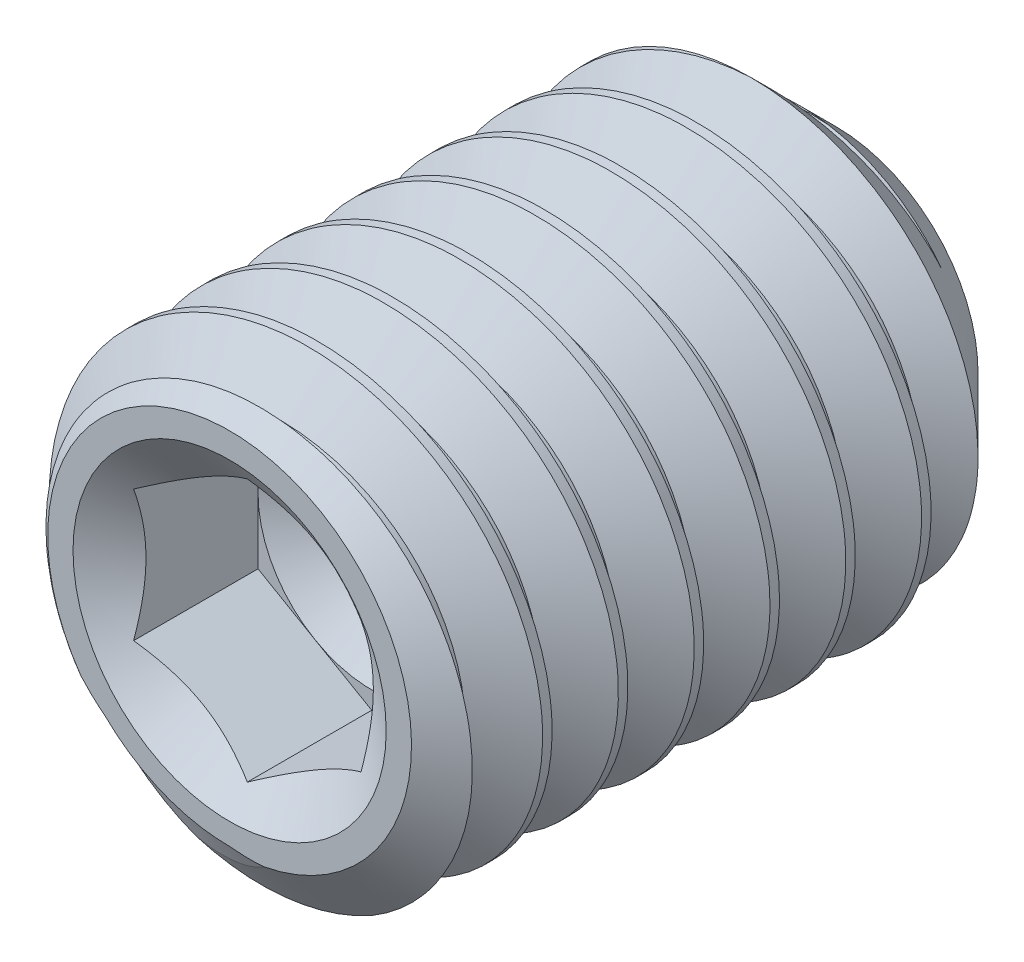
SolidWorks part; units mm, degrees
ref_plane "Front Plane" through (0, 0, 0) normal (0, 0, 1) x (1, 0, 0)
ref_plane "Top Plane" through (0, 0, 0) normal (0, 1, 0) x (1, 0, 0)
ref_plane "Right Plane" through (0, 0, 0) normal (1, 0, 0) x (0, 0, -1)
sketch "Sketch1" plane through (0, 0, 0) normal (1, 0, 0) x (0, 0, -1)
  line L0 (-1.7808, 0) -> (-1.7808, 1.2)
  line L1 (-1.7808, 1.2) -> (-1.5708, 1.5)
  line L2 (-1.5708, 1.5) -> (1.6567, 1.5)
  line L3 (1.6567, 1.5) -> (2.2192, 0.9375)
  line L5 (1.7808, 0) -> (-1.7808, 0)
  line L6 (1.7808, 0) -> (2.2192, 0) construction
  line L7 (2.2192, 0) -> (2.2192, 0.9375) construction
  line L8 (2.2192, -0.9375) -> (1.7808, 0) construction
  line L9 (-1.5708, -1.5) -> (1.6567, -1.5) construction
  line L10 (0, 0) -> (0, -0.5) construction
  line L11 (1.7808, 0) -> (2.112, 0.5512)
  line L12 (1.7808, 0) -> (2.112, -0.5512) construction
  arc A0 (2.112, 0.5512) -> (2.2192, 0.9375) centre (1.4692, 0.9375) ccw
  arc A1 (2.112, -0.5512) -> (2.2192, -0.9375) centre (1.4692, -0.9375) cw construction
  point P11 (-1.7808, 1.5)
  point P12 (0.4692, -1.5)
  point P13 (-0.5308, -1.5)
  point P14 (2.2192, 1.5)
  dimension "D5" = 0.75
  dimension "Thread Size" = 3
  dimension "Length" = 4
  dimension "D3" = 35
  dimension "D6" = 45
  dimension "D7" = 2.4
  dimension "Thread Pitch" = 0.5
  dimension "D2" = 1.25
  dimension "D4" = 59
  dimension "D8" = 1.875
  dimension "D1" = 1.75
sketch "Sketch2" plane through (0, 0, 0) normal (0, 0, 1) x (1, 0, 0)
  line L1 (0.75, 0.433) -> (0, 0.866) construction
  line L2 (0, 0.866) -> (-0.75, 0.433) construction
  line L3 (-0.75, 0.433) -> (-0.75, -0.433) construction
  line L4 (-0.75, -0.433) -> (0, -0.866) construction
  line L5 (0, -0.866) -> (0.75, -0.433) construction
  line L6 (0.75, -0.433) -> (0.75, 0.433) construction
  circle A0 centre (0, 0) radius 0.75 construction
  circle A1 centre (0, 0) radius 1.5 construction
  dimension "Drive Size" = 1.5
sketch "Sketch4" plane through (0, 0, 0) normal (1, 0, 0) x (0, 0, -1)
  line L0 (1.7808, 0) -> (2.112, 0.5512) construction
  line L1 (-1.5708, 1.5) -> (1.6567, 1.5) construction
  line L2 (-1.7808, 0) -> (-1.7808, 1.2) construction
  line L3 (1.7808, 0) -> (-1.7808, 0) construction
  line L4 (1.7808, 0) -> (2.112, 0.5512)
  line L5 (1.6567, 1.5) -> (2.2192, 0.9375) construction
  line L6 (1.6567, 1.5) -> (2.2192, 0.9375)
  line L8 (1.7808, 0) -> (-1.7808, 0)
  line L9 (-1.7808, 0) -> (-1.7808, 1.2)
  line L10 (-1.5708, 1.5) -> (1.6567, 1.5)
  line L11 (-1.7808, 1.2) -> (-1.5708, 1.5) construction
  line L12 (-1.7808, 1.2) -> (-1.5708, 1.5)
  arc A0 (2.112, 0.5512) -> (2.2192, 0.9375) centre (1.4692, 0.9375) ccw construction
  arc A1 (2.112, 0.5512) -> (2.2192, 0.9375) centre (1.4692, 0.9375) ccw
revolve "Revolve1" add sketch "Sketch4" angle 360 about L8
sketch "Sketch6" plane through (0, 0, 1.7808) normal (0, 0, 1) x (1, 0, 0)
  line L1 (0.75, 0.433) -> (0, 0.866)
  line L2 (0, 0.866) -> (-0.75, 0.433)
  line L3 (-0.75, 0.433) -> (-0.75, -0.433)
  line L4 (-0.75, -0.433) -> (0, -0.866)
  line L5 (0, -0.866) -> (0.75, -0.433)
  line L6 (0.75, -0.433) -> (0.75, 0.433)
  circle A0 centre (0, 0) radius 0.75 construction
  dimension "D1" = 1.5
extrude "Cut-Extrude3" cut sketch "Sketch6" against normal blind 0.9375
sketch "Sketch7" plane through (0, 0, 1.7808) normal (0, 0, 1) x (1, 0, 0)
  line L0 (0, 0.866) -> (0, 1.2) construction
  circle A0 centre (0, 0) radius 1.033
  circle A2 centre (0, 0) radius 1.2 construction
  point P6 (0, 1.033)
  point P10 (0, 1.033)
extrude "Cut-Extrude4" cut sketch "Sketch7" against normal through all draft 55
sketch "Sketch8" plane through (0, 0, 0.8433) normal (0, 0, 1) x (1, 0, 0)
  circle A0 centre (0, 0) radius 0.75 construction
  circle A1 centre (0, 0) radius 0.75
extrude "Cut-Extrude5" cut sketch "Sketch8" against normal through all draft 60
ref_plane "Plane1" through (0, 0, -2.2192) normal (0, 0, 1) x (1, 0, 0)
sketch "Sketch9" plane through (0, 0, -2.2192) normal (0, 0, 1) x (1, 0, 0)
  circle A0 centre (0, 0) radius 1.5 construction
  circle A1 centre (0, 0) radius 1.5
curve "Helix/Spiral1" pitch 0.5 height 4.5 radius 1.5 centre (0, 0, -2.2192) axis (0, 0, 1) start towards (0, 1, 0)
sketch "Sketch10" plane through (0, 0, 0) normal (1, 0, 0) x (0, 0, -1)
  line L0 (2.2192, 1.5) -> (2.6567, 1.5)
  line L1 (2.6567, 1.5) -> (2.4692, 1.1752)
  line L2 (2.4067, 1.1752) -> (2.2192, 1.5)
  line L3 (2.4067, 1.1752) -> (2.4692, 1.1752)
  line L4 (2.4379, 1.1752) -> (2.4379, 1.5) construction
  line L5 (2.3129, 1.3376) -> (2.5629, 1.3376) construction
  point P10 (2.4379, 1.3376)
  dimension "D1" = 60
  dimension "D2" = 0.0625
  dimension "D3" = 0.25
sweep "Cut-Sweep1" cut profiles "Sketch10" path "Helix/Spiral1"
equation "\"D7@Sketch1\" = \"Thread Size@Sketch1\" * .8"
equation "\"D3\"= \"Length@Sketch1\" + \"Thread Pitch@Sketch1\""
equation "\"D4\"= \"Thread Pitch@Sketch1\""
equation "\"D1@Sketch6\"=\"Drive Size@Sketch2\""
equation "\"D1@Cut-Extrude3\"=\"Drive Size@Sketch2\"*.625"
equation "\"D3@Helix/Spiral1\"=\"Length@Sketch1\"+\"Thread Pitch@Sketch1\""
equation "\"D4@Helix/Spiral1\"=\"Thread Pitch@Sketch1\""
equation "\"D2@Sketch10\"=\"Thread Pitch@Sketch1\"/8"
equation "\"D3@Sketch10\"=\"Thread Pitch@Sketch1\"/2"
equation "\"D2@Sketch1\"=\"Thread Pitch@Sketch1\"*2.5"
equation "\"D5@Sketch1\"=\"Thread Size@Sketch1\"*.25"
equation "\"D8@Sketch1\"=\"Thread Size@Sketch1\"*.625"
equation "\"D1@Sketch1\"=\"Thread Pitch@Sketch1\"*3.5"
